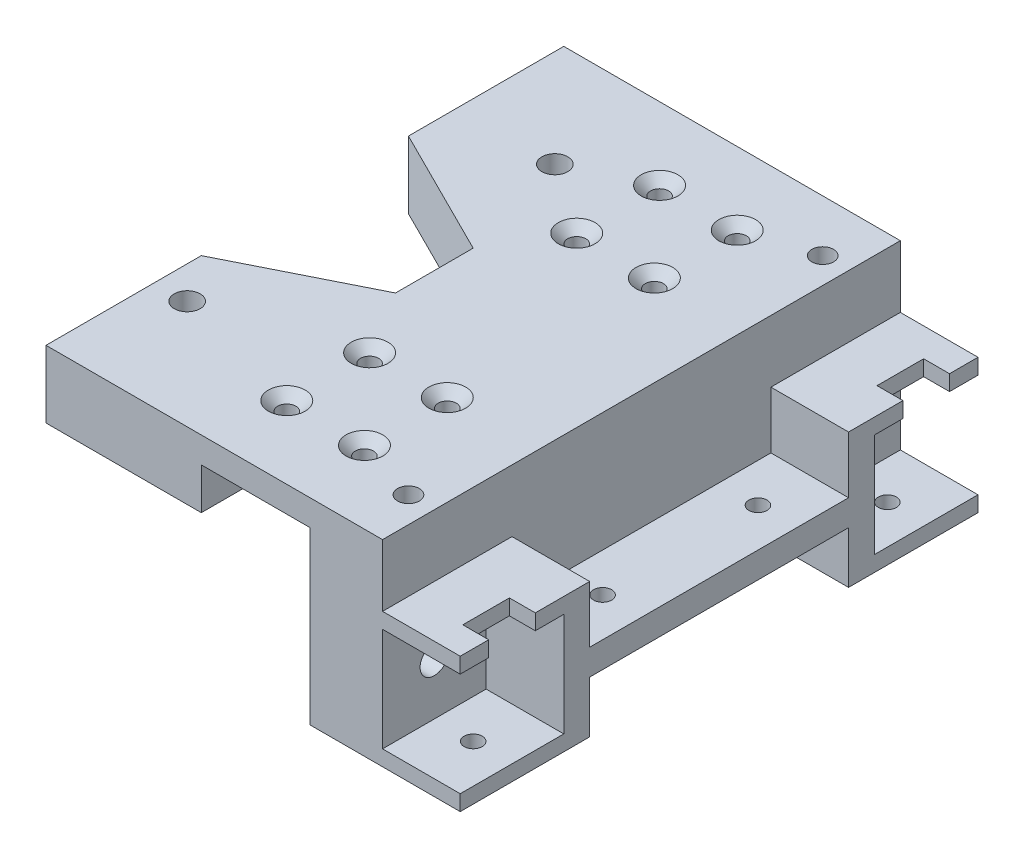
SolidWorks part; units mm, degrees
ref_plane "Front Plane" through (0, 0, 0) normal (0, 0, 1) x (1, 0, 0)
ref_plane "Top Plane" through (0, 0, 0) normal (0, 1, 0) x (1, 0, 0)
ref_plane "Right Plane" through (0, 0, 0) normal (1, 0, 0) x (0, 0, -1)
sketch "Sketch1" plane through (0, 0, 0) normal (0, 1, 0) x (1, 0, 0)
  line L0 (0, 50) -> (0, -50) construction
  line L1 (-10, 50) -> (10, 50)
  line L2 (-10, 50) -> (-10, -50)
  line L3 (-10, -50) -> (10, -50)
  line L4 (10, 50) -> (10, -50) construction
  line L5 (-10, 50) -> (10, -50) construction
  line L6 (-10, -50) -> (10, 50) construction
  line L7 (-7.5, 36) -> (7.5, 36) construction
  line L8 (-7.5, 36) -> (7.5, 20) construction
  line L9 (-10, 0) -> (10, 0) construction
  line L10 (-7.5, -36) -> (7.5, -20) construction
  line L11 (-7.5, -36) -> (7.5, -36) construction
  line L12 (-7.5, 20) -> (7.5, 20) construction
  line L13 (10, 50) -> (11, 50)
  line L14 (11, 50) -> (11, -50)
  line L15 (11, -50) -> (10, -50)
  circle A0 centre (-7.5, 36) radius 1.75
  circle A1 centre (7.5, 36) radius 1.75
  circle A2 centre (-7.5, 20) radius 1.75
  circle A3 centre (7.5, 20) radius 1.75
  circle A4 centre (7.5, -20) radius 1.75
  circle A5 centre (-7.5, -20) radius 1.75
  circle A6 centre (7.5, -36) radius 1.75
  circle A7 centre (-7.5, -36) radius 1.75
  point P0 (0, 0)
  point P16 (0, 36)
  dimension "D2" = 3.5
  dimension "D1" = 20
  dimension "D3" = 15
  dimension "D4" = 16
  dimension "D5" = 100
  dimension "D6" = 20
  dimension "D7" = 1
extrude "Boss-Extrude1" add sketch "Sketch1" along normal blind 5
sketch "Sketch2" plane through (11, 0, 0) normal (1, 0, 0) x (0, 0, -1)
  line L1 (-50, 5) -> (50, 5)
  line L2 (-50, 5) -> (-50, -33)
  line L3 (-50, -33) -> (50, -33)
  line L5 (50, 5) -> (50, -33)
  line L6 (50, 5) -> (50, 0) construction
  line L7 (-50, 5) -> (-50, 0) construction
  line L8 (-50, 5) -> (50, 5) construction
  dimension "D1" = 38
extrude "Boss-Extrude2" add sketch "Sketch2" along normal blind 14
sketch "Sketch3" plane through (25, 0, 0) normal (1, 0, 0) x (0, 0, -1)
  line L0 (0, 5) -> (0, -33) construction
  line L1 (-25, -18) -> (25, -18)
  line L2 (-25, -18) -> (-25, -23)
  line L3 (-25, -23) -> (25, -23)
  line L4 (25, -18) -> (25, -23)
  line L5 (50, 5) -> (-50, 5) construction
  line L6 (-50, -33) -> (50, -33) construction
  point P10 (0, -18)
  dimension "D1" = 5
  dimension "D2" = 50
  dimension "D3" = 10
extrude "Boss-Extrude3" add sketch "Sketch3" along normal blind 15
sketch "Sketch4" plane through (0, -18, 0) normal (0, 1, 0) x (1, 0, 0)
  line L0 (25, 0) -> (40, 0) construction
  line L1 (25, 25) -> (25, -25) construction
  line L2 (40, 25) -> (40, -25) construction
  line L3 (32.5, -15) -> (32.5, 15) construction
  circle A0 centre (32.5, 15) radius 1.75
  circle A1 centre (32.5, -15) radius 1.75
  point P8 (32.5, 0)
  dimension "D1" = 30
  dimension "D2" = 3.5
extrude "Cut-Extrude1" cut sketch "Sketch4" against normal through all
sketch "Sketch8" plane through (25, 0, 0) normal (1, 0, 0) x (0, 0, -1)
  line L0 (-50, 5) -> (-50, -33) construction
  line L1 (-50, -7) -> (-25, -7)
  line L2 (-50, -7) -> (-50, -10)
  line L3 (-50, -33) -> (-25, -33)
  line L4 (-25, -7) -> (-25, -33)
  line L5 (-50, -30) -> (-50, -33)
  line L6 (-50, -30) -> (-30, -30)
  line L8 (-50, -10) -> (-30, -10)
  line L9 (-30, -30) -> (-30, -10)
  line L10 (0, 20.9) -> (0, -20.9) construction
  line L11 (30, -30) -> (30, -10)
  line L12 (50, -10) -> (30, -10)
  line L13 (50, -30) -> (30, -30)
  line L14 (50, -30) -> (50, -33)
  line L15 (25, -7) -> (25, -33)
  line L16 (50, -33) -> (25, -33)
  line L17 (50, -7) -> (50, -10)
  line L18 (50, -7) -> (25, -7)
  line L19 (-50, -33) -> (50, -33) construction
  dimension "D1" = 3
  dimension "D2" = 5
  dimension "D3" = 3
  dimension "D4" = 20
  dimension "D5" = 20
extrude "Boss-Extrude6" add sketch "Sketch8" along normal blind 15
sketch "Sketch9" plane through (25, 0, 0) normal (1, 0, 0) x (0, 0, -1)
  line L0 (-50, -10) -> (-30, -30) construction
  line L1 (50, -10) -> (30, -30) construction
  circle A0 centre (-40, -20) radius 2.75
  circle A1 centre (40, -20) radius 2.75
  dimension "D1" = 5.5
extrude "Cut-Extrude3" cut sketch "Sketch9" against normal through all
sketch "Sketch10" plane through (11, 0, 0) normal (-1, 0, 0) x (0, 0, 1)
  circle A0 centre (-40, -20) radius 4.5
  circle A1 centre (40, -20) radius 4.5
  dimension "D1" = 9
extrude "Cut-Extrude4" cut sketch "Sketch10" against normal offset from surface (9 mm away) 5 up to face at (25, -20, 37.25)
sketch "Sketch11" plane through (0, -7, 0) normal (0, 1, 0) x (1, 0, 0)
  line L0 (40, -25) -> (40, -50) construction
  line L1 (40, -35.5) -> (35, -35.5)
  line L2 (40, -35.5) -> (40, -44.5)
  line L3 (40, -44.5) -> (35, -44.5)
  line L4 (35, -35.5) -> (35, -44.5)
  line L5 (35, -40) -> (40, -40) construction
  line L6 (40, -50) -> (25, -50) construction
  line L7 (-10, 0) -> (40, 0) construction
  line L8 (-10, 50) -> (-10, -50) construction
  line L9 (40, 25) -> (40, -25) construction
  line L10 (40, -35.5) -> (35, -35.5)
  line L11 (40, -44.5) -> (35, -44.5)
  line L12 (35, 40) -> (40, 40) construction
  line L13 (40, 44.5) -> (35, 44.5)
  line L14 (40, 35.5) -> (35, 35.5)
  line L15 (35, 35.5) -> (35, 44.5)
  line L16 (40, 44.5) -> (35, 44.5)
  line L17 (40, 35.5) -> (40, 44.5)
  line L18 (40, 35.5) -> (35, 35.5)
  line M7 (40, -50) -> (40, -25)
  dimension "D1" = 9
  dimension "D2" = 10
  dimension "D3" = 5
extrude "Cut-Extrude5" cut sketch "Sketch11" against normal up to next contours L1 L4 L3 M7 | L14 L17 L13 L15 region at (37.5, -7, 40) region at (37.5, -7, -40)
sketch "Sketch12" plane through (0, -30, 0) normal (0, 1, 0) x (1, 0, 0)
  line L0 (40, -40) -> (25, -40) construction
  line L1 (40, -30) -> (40, -50) construction
  line L2 (25, -25) -> (25, -50) construction
  line L3 (-20.9, 0) -> (20.9, 0) construction
  circle A0 centre (32.5, -40) radius 1.75
  circle A2 centre (32.5, 40) radius 1.75
  dimension "D1" = 3.5
extrude "Cut-Extrude6" cut sketch "Sketch12" against normal through all
sketch "Sketch13" plane through (-10, 0, 0) normal (-1, 0, 0) x (0, 0, 1)
  line L1 (-50, 5) -> (50, 5)
  line L2 (-50, 5) -> (-50, -8)
  line L3 (-50, -8) -> (50, -8)
  line L4 (50, 5) -> (50, -8)
  dimension "D1" = 13
extrude "Boss-Extrude7" add sketch "Sketch13" along normal blind 30
sketch "Sketch14" plane through (0, 5, 0) normal (0, 1, 0) x (1, 0, 0)
  line L0 (-40, -50) -> (25, -50) construction
  line L1 (-10.5, -50) -> (10.5, -50) construction
  line L2 (-10.5, -50) -> (-10.5, 50) construction
  line L3 (-10.5, 50) -> (10.5, 50) construction
  line L4 (10.5, -50) -> (10.5, 50) construction
  line L5 (25, 50) -> (-40, 50) construction
  line L6 (-27.23, 29.42) -> (-27.23, -29) construction
  line L12 (-33.73, -35.5) -> (40, -35.5) construction
  line L18 (-21.15, 35.5) -> (40, 35.5) construction
  circle A0 centre (-21.15, 29.42) radius 2.5
  circle A1 centre (-33.73, -29) radius 2.5
  circle A2 centre (-33.73, -29) radius 6.5 construction
  circle A3 centre (-21.15, 29.42) radius 6.08 construction
  point P14 (0, 50)
  dimension "D1" = 5
  dimension "D2" = 5
  dimension "D4" = 21
  dimension "D5" = 13
  dimension "D6" = 12.16
  dimension "D3" = 21.15
extrude "Cut-Extrude7" cut sketch "Sketch14" against normal through all
sketch "Sketch15" plane through (0, -8, 0) normal (0, -1, 0) x (1, 0, 0)
  line L0 (-40, -50) -> (-40, 50) construction
  line L1 (-29.73, 26.6906) -> (-29.73, 31.3094)
  line L2 (-29.73, 31.3094) -> (-33.73, 33.6188)
  line L3 (-33.73, 33.6188) -> (-37.73, 31.3094)
  line L4 (-37.73, 31.3094) -> (-37.73, 26.6906)
  line L5 (-37.73, 26.6906) -> (-33.73, 24.3812)
  line L6 (-33.73, 24.3812) -> (-29.73, 26.6906)
  line L7 (-25.15, -31.7294) -> (-21.15, -34.0388)
  line L8 (-21.15, -34.0388) -> (-17.15, -31.7294)
  line L9 (-17.15, -31.7294) -> (-17.15, -27.1106)
  line L10 (-17.15, -27.1106) -> (-21.15, -24.8012)
  line L11 (-21.15, -24.8012) -> (-25.15, -27.1106)
  line L12 (-25.15, -27.1106) -> (-25.15, -31.7294)
  circle A0 centre (-33.73, 29) radius 4 construction
  circle A1 centre (-21.15, -29.42) radius 4 construction
  dimension "D1" = 8
extrude "Cut-Extrude8" cut sketch "Sketch15" against normal blind 4
sketch "Sketch16" plane through (0, 5, 0) normal (0, 1, 0) x (1, 0, 0)
  line L0 (20, 40) -> (40, 40) construction
  line L1 (40, 50) -> (40, 30) construction
  line L2 (20, -40) -> (40, -40) construction
  line L3 (40, -30) -> (40, -50) construction
  circle A0 centre (20, 40) radius 2.1
  circle A1 centre (20, -40) radius 2.1
  dimension "D1" = 4.2
  dimension "D2" = 4.2
  dimension "D3" = 20
extrude "Cut-Extrude9" cut sketch "Sketch16" against normal blind 4
chamfer "Chamfer1" distance 1.8 angle 45 8 edges at (-7.5, 5, -34.25) (7.5, 5, -34.25) (-7.5, 5, -18.25) (7.5, 5, -18.25) (-7.5, 5, 18.25) (7.5, 5, 18.25) (-7.5, 5, 34.25) (7.5, 5, 34.25)
sketch "Sketch17" plane through (0, 5, 0) normal (0, 1, 0) x (1, 0, 0)
  line L0 (-40, 20) -> (-15, 7.5)
  line L1 (-40, -50) -> (-40, 50) construction
  line L2 (-15, 7.5) -> (-15, -7.5)
  line L3 (-15, -7.5) -> (-40, -20)
  line L4 (-40, -20) -> (-40, 20)
  point P6 (-15, 0)
  dimension "D1" = 15
  dimension "D2" = 40
  dimension "D3" = 15
extrude "Cut-Extrude10" cut sketch "Sketch17" against normal through all
